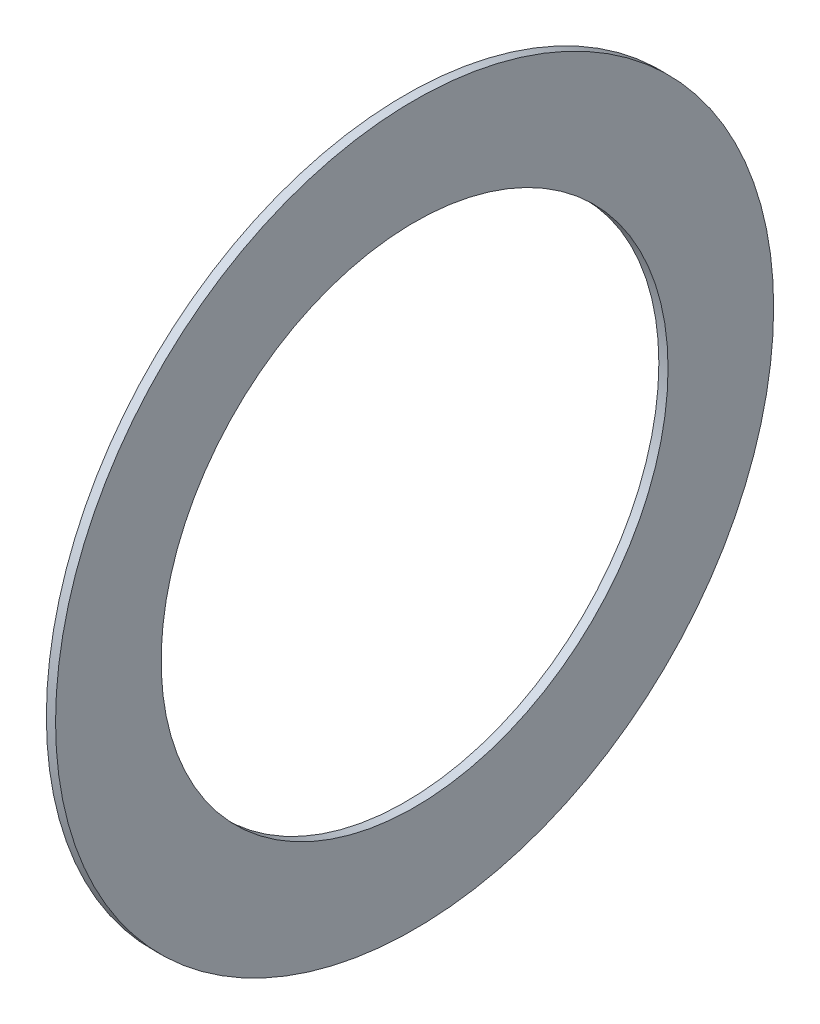
SolidWorks part; units mm, degrees
ref_plane "Front Plane" through (0, 0, 0) normal (0, 0, 1) x (1, 0, 0)
ref_plane "Top Plane" through (0, 0, 0) normal (0, 1, 0) x (1, 0, 0)
ref_plane "Right Plane" through (0, 0, 0) normal (1, 0, 0) x (0, 0, -1)
sketch "Sketch1" plane through (0, 0, 0) normal (1, 0, 0) x (0, 0, -1)
  circle A0 centre (0, 0) radius 39
  circle A1 centre (0, 0) radius 27.5 construction
  circle A2 centre (0, 0) radius 27.53
  dimension "OD" = 78
  dimension "For Shaft Diameter" = 55
  dimension "ID" = 55.06
sketch "Sketch2" plane through (0, 0, 0) normal (0, 0, 1) x (1, 0, 0)
  line L0 (0.5, 0) -> (-0.5, 0) construction
  line L1 (0.5, -39) -> (-0.5, -39) construction
  line L2 (0.5, -39) -> (0.5, 39) construction
  line L3 (0.5, 39) -> (-0.5, 39) construction
  line L4 (-0.5, -39) -> (-0.5, 39) construction
  point P6 (0, 39)
  point P9 (0, -39)
  dimension "Thickness" = 1
sketch "Sketch3" plane through (0, 0, 0) normal (1, 0, 0) x (0, 0, -1)
  circle A1 centre (0, 0) radius 39 construction
  circle A3 centre (0, 0) radius 39
  circle A4 centre (0, 0) radius 27.53 construction
  circle A5 centre (0, 0) radius 27.53
extrude "Boss-Extrude1" add sketch "Sketch3" along normal up to vertex (0.5 mm away) and the other way up to vertex (0.5 mm away) up to point (0.5, 39, 0) other way up to point (-0.5, 39, 0)
